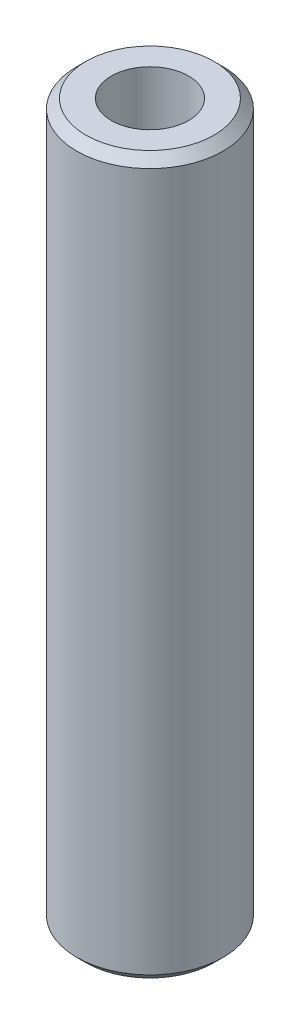
SolidWorks part; units mm, degrees
ref_plane "Front Plane" through (0, 0, 0) normal (0, 0, 1) x (1, 0, 0)
ref_plane "Top Plane" through (0, 0, 0) normal (0, 1, 0) x (1, 0, 0)
ref_plane "Right Plane" through (0, 0, 0) normal (1, 0, 0) x (0, 0, -1)
sketch "Sketch1" plane through (0, 0, 0) normal (0, 1, 0) x (1, 0, 0)
  circle A0 centre (0, 0) radius 10
  dimension "SHAFT_OD" = 20
extrude "Boss-Extrude1" add sketch "Sketch1" along normal blind 97.8815
sketch "Sketch2" plane through (0, 0, 0) normal (0, 1, 0) x (1, 0, 0)
  circle A0 centre (0, 0) radius 5.2747
  dimension "BORE_D" = 10.5494
extrude "Cut-Extrude1" cut sketch "Sketch2" along normal through all
chamfer "Chamfer1" distance 1.2571 angle 45 2 edges at (0, 97.8815, 10) (0, 0, 10)
